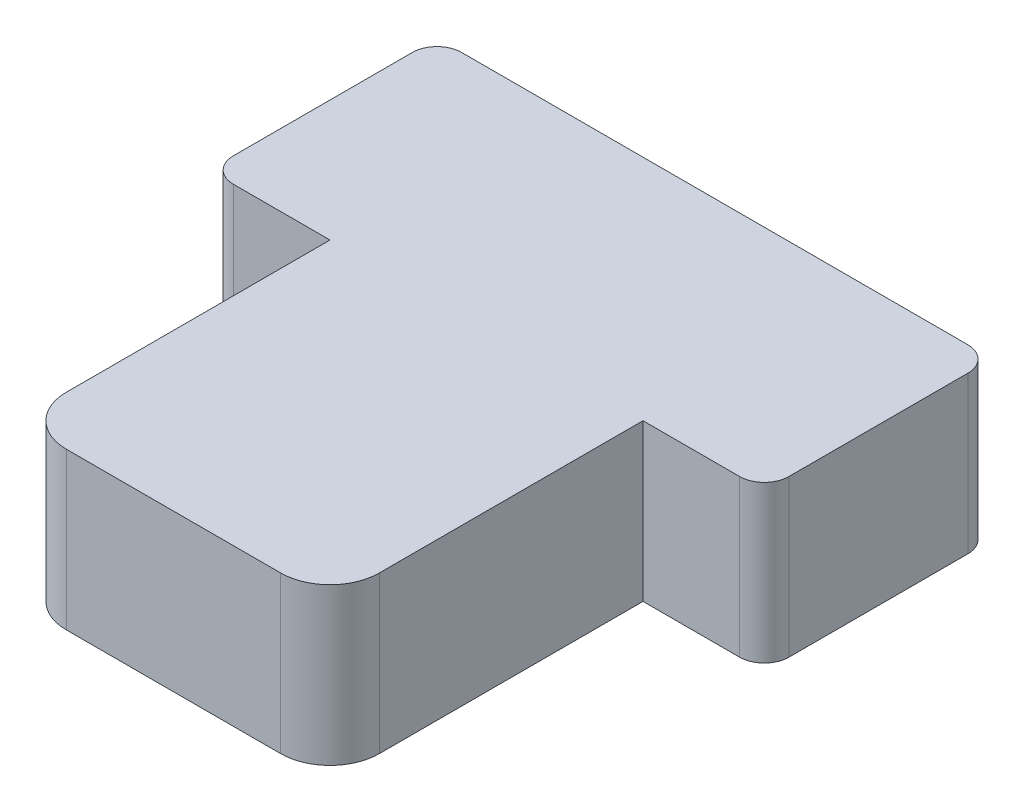
SolidWorks part; units mm, degrees
material "Beech"
ref_plane "Front Plane" through (0, 0, 0) normal (0, 0, 1) x (1, 0, 0)
ref_plane "Top Plane" through (0, 0, 0) normal (0, 1, 0) x (1, 0, 0)
ref_plane "Right Plane" through (0, 0, 0) normal (1, 0, 0) x (0, 0, -1)
sketch "Sketch1" plane through (0, 0, 0) normal (0, 1, 0) x (1, 0, 0)
  line L0 (0, 0) -> (6.35, 0)
  line L1 (0, 0) -> (0, 6.35)
  line L2 (6.35, 0) -> (6.35, 6.35)
  line L4 (-2.46, 10.9807) -> (-2.46, 6.35)
  line L5 (-2.46, 10.9807) -> (8.81, 10.9807)
  line L6 (-2.46, 6.35) -> (0, 6.35)
  line L7 (8.81, 10.9807) -> (8.81, 6.35)
  line L8 (6.35, 6.35) -> (8.81, 6.35)
  dimension "D1" = 6.35
  dimension "D2" = 6.35
  dimension "D3" = 11.27
  dimension "D4" = 4.6307
extrude "MotorSupport_Extrude" add sketch "Sketch1" along normal blind 3.175
fillet "MotorSupport_BottomFillet" radius 1 2 edges at (0, 1.5875, 0) (6.35, 1.5875, 0)
fillet "MotorSupport_TopFillet" radius 0.5 4 edges at (-2.46, 1.5875, -6.35) (-2.46, 1.5875, -10.9807) (8.81, 1.5875, -10.9807) (8.81, 1.5875, -6.35)
equation "\"CageLeftBottomEdge\"=22.11mm"
equation "\"CageLeftTopEdge\"=22.11mm"
equation "\"CageRightBottomEdge\"=21.63mm"
equation "\"CageRightTopEdge\"=21.63mm"
equation "\"CageHeight\"=86.04mm"
equation "\"CageLength\"=73.76mm"
equation "\"CageTopScrewClearance\"=10mm"
equation "\"CageBottomScrewClearance\"=25mm"
equation "\"CageLeftTopDepth\"= 11.65mm"
equation "\"CageLeftBottomDepth\"=11.11mm"
equation "\"CageLeftTopHeight\"=8.56175mm"
equation "\"CageLeftBottomHeight\"=16mm"
equation "\"CageRightTopDepth\"= 11.05mm"
equation "\"CageRightBottomDepth\"=10.58mm"
equation "\"CageRightTopHeight\"=9.6mm"
equation "\"CageRightBottomHeight\"=15.49mm"
equation "\"CageLeftTopChannelDepth\"=2.41908mm"
equation "\"CageLeftBottomChannelDepth\"=2.588mm"
equation "\"CageLeftChannelHeight\"=11.7mm"
equation "\"CageRightTopChannelDepth\"=2.32mm"
equation "\"CageRightBottomChannelDepth\"=2.318mm"
equation "\"CageRightChannelHeight\"=10mm"
equation "\"CageChanRelHeight\"=23.99mm"
equation "\"CageChanRelDepth\"=5.492mm"
equation "\"CageChamberRadius\"=16.261mm"
equation "\"CageScrewDiameter\"=4.8mm"
equation "\"CageSetScrewDiameter\"=3.5mm"
equation "\"CageAxleRadius\"=6.639mm"
equation "\"CageAxleKeyHeight\"=1.619mm"
equation "\"CageAxleKeyWidth\"=2.662mm"
equation "\"CageHoseWindowWidth\"=16.29mm"
equation "\"CageHoseWindowHeight\"=26.5mm"
equation "\"CageHoseWindow-Edge\"=8.89mm"
equation "\"CageScrew-VerticalEdge\"=5.0mm"
equation "\"CageScrew-HorizontalEdge\"=7.5mm"
equation "\"CageScrew-HoseCornerScrewEdge\"=4.45mm"
equation "\"CageAxle-BottomEdge\"=56.05mm"
equation "\"CageAxle-FrontEdge\"=46.03mm"
equation "\"CageBackSetScrew-Axle\"=40mm"
equation "\"CageFrontSetScrew-Axle\"=22mm"
equation "\"CageVelocityWindow-BackEdge\"=34.8mm"
equation "\"CageVelocityWindow-BottomEdge\"=27.55mm"
equation "\"CageVelocityWindowHeight\"=22.29mm"
equation "\"CageVelocityWindowWidth\"=12.61mm"
equation "\"TriggerSlot-BottomEdge\"=6.35mm"
equation "\"TriggerSlot-FrontEdge\"=15mm"
equation "\"TriggerSlotSize\"=6.7mm"
equation "\"TriggerRackOffset\"=.236224in"
equation "\"TriggerSlotSizeInt\"=.25in"
equation "\"MotorMountLegLength\"=.25in"
equation "\"GearOffset\"=.264907in"
equation "\"TriggerSlotSpacing\"=.25in"
equation "\"TGMGearFaceDiameter\"=24.40mm"
equation "\"TGMCylinderLength\"=15.00mm"
equation "\"TGMScrewHole-Center\"=8.70mm"
equation "\"TGMScrewHoleDiameter\"=5.04mm"
equation "\"TGMCenterHoleDiameter\"=9.50mm"
equation "\"TGMShaftCollarSideLength\"=19.00mm"
equation "\"TGMShaftCollarDockingDepth\"=7.00mm"
equation "\"whitemotordepth\"=11.27mm"
equation "\"whitemotorbackdepth\"=3.845mm"
equation "\"whitemotoraxledepth\" = 3.5mm"
equation "\"whitemotoraxleoffset\"=11.4mm"
equation "\"whitemotorwidth\"=12.07mm"
equation "\"whitemotorheight\"=16.68mm"
equation "\"whitemotorcylinderlength\" =13.04mm"
equation "\"whitemotorcylinderradius\"=3.845mm"
equation "\"whitemotorcylinderoffset\"=2.35mm"
equation "\"whitemotorcutoutlength\"=1.88mm"
equation "\"whitemotorouterrad\"=5mm"
equation "\"whitemotorinnerrad\"=2.95mm"
equation "\"D1@Sketch1\"=\"TriggerSlotSizeInt\""
equation "\"D2@Sketch1\"=\"MotorMountLegLength\""
equation "\"D3@Sketch1\"=\"whitemotordepth\""
equation "\"D4@Sketch1\"=\"GearOffset\"+\"TriggerRackOffset\"-\"whitemotoraxleoffset\"+\"elasticdepth\"+.005in"
equation "\"D1@MotorSupport_Extrude\"=.125in"
equation "\"TriggerMiniSlotWidth\"=3.5mm"
equation "\"TriggerRackWidth\"=6.5mm"
equation "\"elasticracklength\"=2in"
equation "\"elasticrackpegsize\"=.25in"
equation "\"elasticrackpegbuffer\"=.125in"
equation "\"elasticrackpegspacing\"=1.76476378in"
equation "\"elasticbaybuffer\"=.25in"
equation "\"elasticdepth\"=.125in"
equation "\"elasticbaydepth\"=.75in"
equation "\"motormountwidth\"=12mm"
equation "\"motormountcornerfillet\"=3mm"
equation "\"pandiscradius\"=14in"
equation "\"towermaterialwidth\"=.25in"
equation "\"towerslotlength\"=.5in"
equation "\"towermarkerspace\"=5in"
equation "\"towerslothorizoffset\"=1in"
equation "\"towerslothorizspacing\"=2in"
equation "\"towerslotvertoffset\"=3in"
equation "\"towerslotvertspacing\"=2in"
equation "\"towerheight\"=12in"
equation "\"towerupslot\"=1in"
equation "\"toweraxle\"=.5in"
equation "\"towerplatslotoffset\"=1.5in"
equation "\"towermotorpanelheight\"=10in"
equation "\"towerplatdepth\"=2in"
equation "\"stepperouterrad\"=10mm"
equation "\"stepperscrewsize\"=3.45mm"
equation "\"stepperscrewc2c\"=49.5mm"
equation "\"stepperdepthoffset\"=24mm"
equation "\"stepperhorizoffset\"=22.91mm"
equation "\"shaftslotOD\"=18.8mm"
equation "\"shaftslotID\"=13.28mm"
equation "\"shaftkeywidth\"=2.67mm"
equation "\"shaftkeydepth\"=1.8mm"
equation "\"shaftcollartotaldepth\"=12.5mm"
equation "\"shaftsquaredepth\"=6mm"
equation "\"shaftsetscrewsize\"=3.5mm"
equation "\"shaftkeytightdepth\"=1.85mm"
equation "\"shaftslottightID\"=12.78mm"
equation "\"shaftsetscrewoffset\"=9mm"
equation "\"cagecollartotaldepth\"=10mm"
equation "\"cagecollartotalwidth\"=35mm"
equation "\"cagecollarbasedepth\"=4mm"
